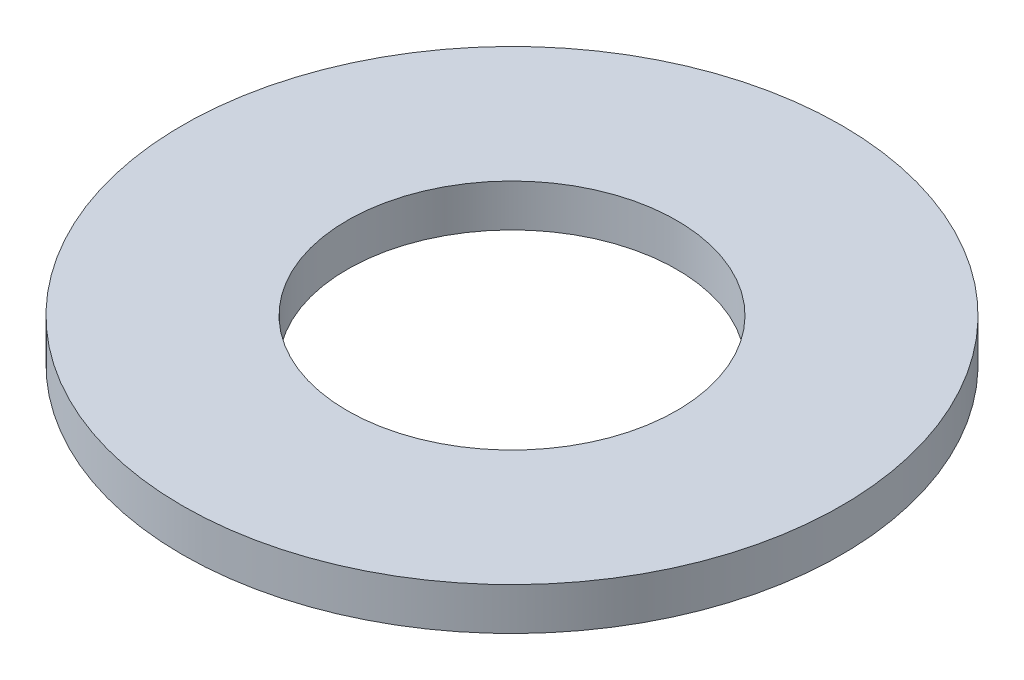
SolidWorks part; units mm, degrees
ref_plane "Front Plane" through (0, 0, 0) normal (0, 0, 1) x (1, 0, 0)
ref_plane "Top Plane" through (0, 0, 0) normal (0, 1, 0) x (1, 0, 0)
ref_plane "Right Plane" through (0, 0, 0) normal (1, 0, 0) x (0, 0, -1)
sketch "Sketch1" plane through (0, 0, 0) normal (0, 1, 0) x (1, 0, 0)
  circle A0 centre (0, 0) radius 70
  dimension "FLANGE_OD" = 140
extrude "Boss-Extrude1" add sketch "Sketch1" along normal blind 9
sketch "Sketch2" plane through (0, 0, 0) normal (0, 1, 0) x (1, 0, 0)
  circle A0 centre (0, 0) radius 35
  dimension "BORE_D" = 70
extrude "Cut-Extrude1" cut sketch "Sketch2" along normal through all
sketch "Sketch3" plane through (0, 9, 0) normal (0, 1, 0) x (1, 0, 0)
  circle A0 centre (0, 0) radius 22.0598 construction
  circle A1 centre (-22.0598, 0) radius 3.386
  dimension "BOLT_D" = 6.772
  dimension "BOLT_PCD" = 44.1197
extrude "Cut-Extrude2" cut sketch "Sketch3" against normal blind 7.0024 rebuild error yes
pattern_circular "CirPattern1" count 6 over 360 rebuild error yes
